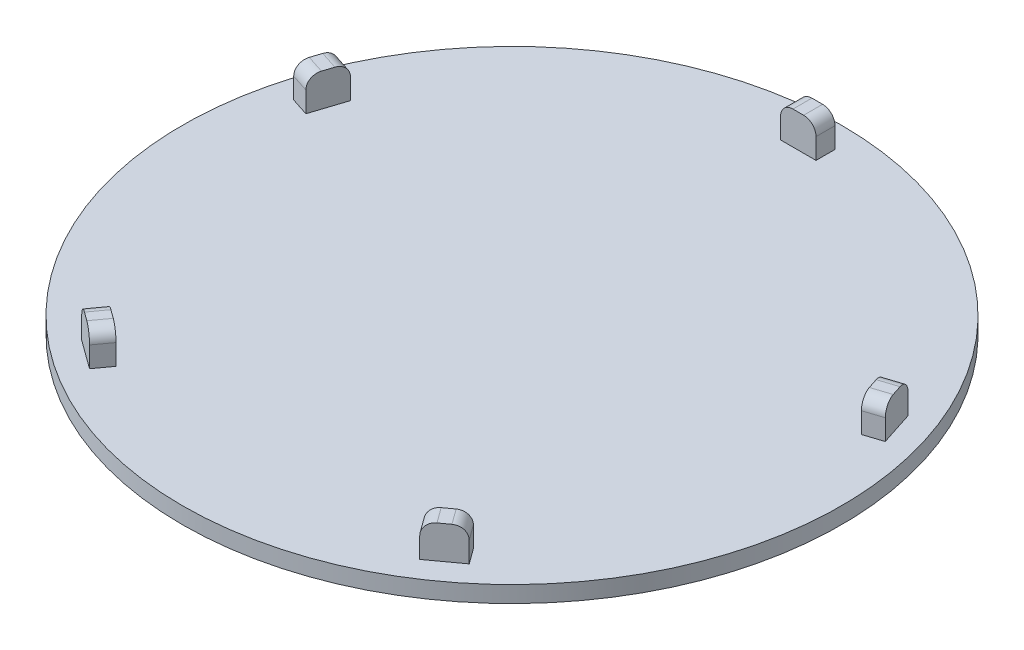
SolidWorks part; units mm, degrees
ref_plane "Front Plane" through (0, 0, 0) normal (0, 0, 1) x (1, 0, 0)
ref_plane "Top Plane" through (0, 0, 0) normal (0, 1, 0) x (1, 0, 0)
ref_plane "Right Plane" through (0, 0, 0) normal (1, 0, 0) x (0, 0, -1)
sketch "Sketch1" plane through (0, 0, 0) normal (0, 1, 0) x (1, 0, 0)
  circle A0 centre (0, 0) radius 40
  dimension "D1" = 80
extrude "Boss-Extrude1" add sketch "Sketch1" along normal blind 2
sketch "Sketch2" plane through (0, 2, 0) normal (0, 1, 0) x (1, 0, 0)
  line L0 (-2.3, 37.2) -> (2.3, 37.2)
  line L1 (-2.3, 37.2) -> (-2.3, 34.6)
  line L2 (2.3, 37.2) -> (2.3, 34.6)
  line L3 (-2.3, 34.6) -> (2.3, 34.6)
  line L4 (-2.3, 37.2) -> (2.3, 34.6) construction
  line L5 (2.3, 37.2) -> (-2.3, 34.6) construction
  line L10 (34.6686, 13.6829) -> (36.09, 9.308)
  line L11 (34.6686, 13.6829) -> (32.1958, 12.8794)
  line L16 (36.09, 9.308) -> (33.6173, 8.5046)
  line L17 (32.1958, 12.8794) -> (33.6173, 8.5046)
  line L18 (34.6686, 13.6829) -> (33.6173, 8.5046) construction
  line L19 (36.09, 9.308) -> (32.1958, 12.8794) construction
  line L20 (23.7264, -28.7435) -> (20.0049, -31.4473)
  line L21 (23.7264, -28.7435) -> (22.1981, -26.6401)
  line L22 (20.0049, -31.4473) -> (18.4766, -29.3439)
  line L23 (22.1981, -26.6401) -> (18.4766, -29.3439)
  line L24 (23.7264, -28.7435) -> (18.4766, -29.3439) construction
  line L25 (20.0049, -31.4473) -> (22.1981, -26.6401) construction
  line L26 (-20.0049, -31.4473) -> (-23.7264, -28.7435)
  line L27 (-20.0049, -31.4473) -> (-18.4766, -29.3439)
  line L28 (-23.7264, -28.7435) -> (-22.1981, -26.6401)
  line L29 (-18.4766, -29.3439) -> (-22.1981, -26.6401)
  line L30 (-20.0049, -31.4473) -> (-22.1981, -26.6401) construction
  line L31 (-23.7264, -28.7435) -> (-18.4766, -29.3439) construction
  line L32 (-36.09, 9.308) -> (-34.6686, 13.6829)
  line L33 (-36.09, 9.308) -> (-33.6173, 8.5046)
  line L34 (-34.6686, 13.6829) -> (-32.1958, 12.8794)
  line L35 (-33.6173, 8.5046) -> (-32.1958, 12.8794)
  line L36 (-36.09, 9.308) -> (-32.1958, 12.8794) construction
  line L37 (-34.6686, 13.6829) -> (-33.6173, 8.5046) construction
  point P1 (0, 35.9)
  point P3 (34.1429, 11.0937)
  point P13 (21.1015, -29.0437)
  point P18 (-21.1015, -29.0437)
  point P23 (-34.1429, 11.0937)
  point P28 (0, 0)
  dimension "D1" = 2.6
  dimension "D2" = 4.6
  dimension "D3" = 34.6
  dimension "D4" = 5
extrude "Boss-Extrude2" add sketch "Sketch2" along normal blind 4
fillet "Fillet1" [suppressed] radius 2
sketch "Sketch3" plane through (0, 0, 0) normal (0, -1, 0) x (1, 0, 0)
  circle A1 centre (0, 0) radius 34
  circle A2 centre (0, 0) radius 36
  circle A3 centre (0, 0) radius 36
  dimension "D1" = 4
  dimension "D2" = 2
extrude "Boss-Extrude3" add sketch "Sketch3" along normal blind 2
fillet "Fillet2" radius 1 2 edges at (0, -2, -36) (0, -2, -34)
sketch "Sketch4" plane through (0, 0, 0) normal (0, -1, 0) x (1, 0, 0)
  line L0 (-1.5, -40) -> (-1.5, -1.5)
  line L1 (-1.5, -40) -> (1.5, -40)
  line L2 (-1.5, 40) -> (1.5, 40)
  line L3 (1.5, -40) -> (1.5, -1.5)
  line L4 (-1.5, -40) -> (1.5, 40) construction
  line L5 (-1.5, 40) -> (1.5, -40) construction
  line L6 (-40, 1.5) -> (-1.5, 1.5)
  line L7 (-40, 1.5) -> (-40, -1.5)
  line L8 (40, 1.5) -> (40, -1.5)
  line L9 (-40, -1.5) -> (-1.5, -1.5)
  line L10 (-40, 1.5) -> (40, -1.5) construction
  line L11 (40, 1.5) -> (-40, -1.5) construction
  line L12 (1.5, -1.5) -> (40, -1.5)
  line L13 (1.5, 1.5) -> (40, 1.5)
  line L14 (-0.0562, 1.5) -> (0.0562, 1.5)
  line L15 (-1.5, 1.5) -> (-1.5, 40)
  line L16 (-1.5, -0.0563) -> (-1.5, 0.0562)
  line L17 (-0.0563, -1.5) -> (0.0563, -1.5)
  line L18 (1.5, -0.0563) -> (1.5, 0.0562)
  line L19 (1.5, 1.5) -> (1.5, 40)
  point P1 (0, 0)
  point P2 (0, 0)
  dimension "D1" = 3
  dimension "D2" = 3
extrude "Cut-Extrude1" cut sketch "Sketch4" along normal up to next contours L3 L12 L8 L13 L19 L2 L15 L6 L7 L9 L0 L1
sketch "Sketch5" plane through (0, 6, 0) normal (0, 1, 0) x (1, 0, 0)
  line L0 (-2.15, 37.05) -> (-2.15, 34.75)
  line L1 (-2.15, 34.75) -> (2.15, 34.75)
  line L2 (2.15, 34.75) -> (2.15, 37.05)
  line L3 (2.15, 37.05) -> (-2.15, 37.05)
  line L8 (34.5723, 13.4939) -> (32.3848, 12.7831)
  line L9 (32.3848, 12.7831) -> (33.7136, 8.6936)
  line L10 (33.7136, 8.6936) -> (35.901, 9.4043)
  line L11 (35.901, 9.4043) -> (34.5723, 13.4939)
  line L16 (34.6686, 13.6829) -> (32.1958, 12.8794)
  line L17 (32.1958, 12.8794) -> (33.6173, 8.5046)
  line L18 (33.6173, 8.5046) -> (36.09, 9.308)
  line L19 (36.09, 9.308) -> (34.6686, 13.6829)
  line L44 (-2.3, 37.2) -> (-2.3, 34.6)
  line L45 (-2.3, 34.6) -> (2.3, 34.6)
  line L46 (2.3, 34.6) -> (2.3, 37.2)
  line L47 (2.3, 37.2) -> (-2.3, 37.2)
  line L48 (-2.3, 37.2) -> (-2.3, 34.6)
  line L49 (-2.3, 34.6) -> (2.3, 34.6)
  line L50 (2.3, 34.6) -> (2.3, 37.2)
  line L51 (2.3, 37.2) -> (-2.3, 37.2)
  line L56 (23.5168, -28.7103) -> (22.1649, -26.8496)
  line L57 (22.1649, -26.8496) -> (18.6862, -29.3771)
  line L58 (18.6862, -29.3771) -> (20.0381, -31.2378)
  line L59 (20.0381, -31.2378) -> (23.5168, -28.7103)
  line L60 (23.7264, -28.7435) -> (22.1981, -26.6401)
  line L61 (22.1981, -26.6401) -> (18.4766, -29.3439)
  line L62 (18.4766, -29.3439) -> (20.0049, -31.4473)
  line L63 (20.0049, -31.4473) -> (23.7264, -28.7435)
  line L64 (-20.0381, -31.2378) -> (-18.6862, -29.3771)
  line L65 (-18.6862, -29.3771) -> (-22.1649, -26.8496)
  line L66 (-22.1649, -26.8496) -> (-23.5168, -28.7103)
  line L67 (-23.5168, -28.7103) -> (-20.0381, -31.2378)
  line L68 (-20.0049, -31.4473) -> (-18.4766, -29.3439)
  line L69 (-18.4766, -29.3439) -> (-22.1981, -26.6401)
  line L70 (-22.1981, -26.6401) -> (-23.7264, -28.7435)
  line L71 (-23.7264, -28.7435) -> (-20.0049, -31.4473)
  line L72 (-35.901, 9.4043) -> (-33.7136, 8.6936)
  line L73 (-33.7136, 8.6936) -> (-32.3848, 12.7831)
  line L74 (-32.3848, 12.7831) -> (-34.5723, 13.4939)
  line L75 (-34.5723, 13.4939) -> (-35.901, 9.4043)
  line L76 (-36.09, 9.308) -> (-33.6173, 8.5046)
  line L77 (-33.6173, 8.5046) -> (-32.1958, 12.8794)
  line L78 (-32.1958, 12.8794) -> (-34.6686, 13.6829)
  line L79 (-34.6686, 13.6829) -> (-36.09, 9.308)
  point P66 (0, 0)
  dimension "D4" = 0
  dimension "D5" = 0.15
extrude "Cut-Extrude2" cut sketch "Sketch5" against normal up to surface (4 mm away) up to face at (0, 2, 40)
fillet "Fillet3" radius 1.5 10 edges at (-33.4785, 6, -13.1385) (-34.8073, 6, -9.0489) (-22.8409, 6, 27.78) (-19.3621, 6, 30.3074) (19.3621, 6, 30.3074) (22.8409, 6, 27.78) (34.8073, 6, -9.0489) (33.4785, 6, -13.1385) (-2.15, 6, -35.9) (2.15, 6, -35.9)
